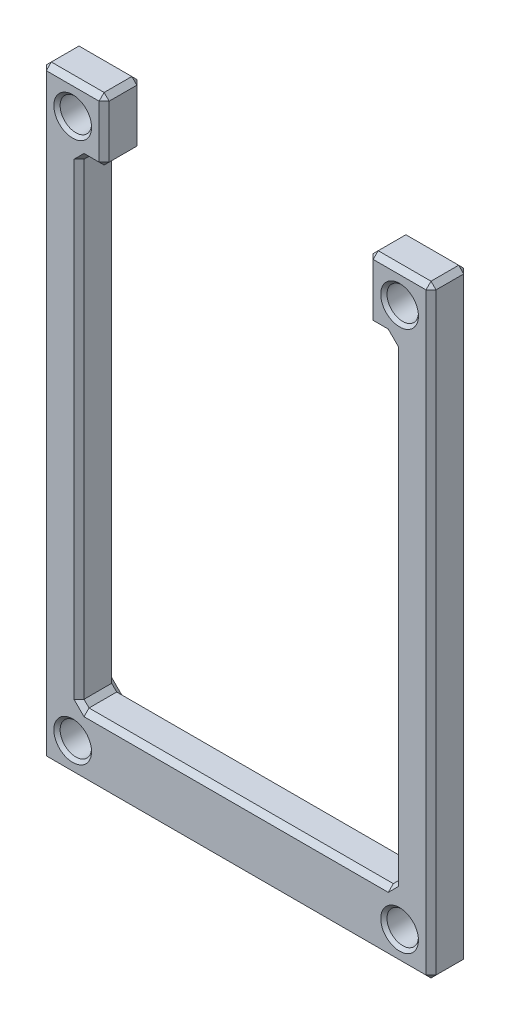
SolidWorks part; units mm, degrees
ref_plane "Ebene vorne" through (0, 0, 0) normal (1, 0, 0) x (0, 1, 0)
ref_plane "Ebene oben" through (0, 0, 0) normal (0, 0, 1) x (0, 1, 0)
ref_plane "Ebene rechts" through (0, 0, 0) normal (0, 1, 0) x (-1, 0, 0)
sketch "Skizze1" plane through (0, 0, 0) normal (0, 0, 1) x (0, 1, 0)
  line L0 (-24, 15.5) -> (24, 15.5)
  line L1 (24, 15.5) -> (24, 10.5)
  line L2 (24, 10.5) -> (-19, 10.5)
  line L3 (-19, 10.5) -> (-19, -10.5)
  line L4 (-19, -10.5) -> (24, -10.5)
  line L5 (24, -10.5) -> (24, -15.5)
  line L6 (24, -15.5) -> (-24, -15.5)
  line L7 (-24, -15.5) -> (-24, 15.5)
  line L8 (0, 15.5) -> (0, 0) construction
  line L9 (-24, 0) -> (0, 0) construction
  dimension "D1" = 48
  dimension "D2" = 31
  dimension "D3" = 5
  dimension "D4" = 5
extrude "Aufsatz-Linear austragen1" add sketch "Skizze1" along normal mid plane 3
hole_wizard "Ø2.5 (2.5) Durchmesser Bohrung1" positions "Skizze2" profile "Skizze3" hole size "Ø2.5" standard "DIN" end condition up to next
sketch "Skizze2" plane through (0, 0, 1.5) normal (0, 0, 1) x (0, -1, 0)
  line L1 (21.5, -13) -> (-21.5, -13) construction
  line L2 (21.5, -13) -> (21.5, 13) construction
  line L3 (21.5, 13) -> (-21.5, 13) construction
  line L4 (-21.5, -13) -> (-21.5, 13) construction
  line L5 (21.5, -13) -> (-21.5, 13) construction
  line L6 (21.5, 13) -> (-21.5, -13) construction
  point P1 (0, 0)
  point P2 (-21.5, 13)
  point P105 (21.5, -13)
  point P106 (21.5, 13)
  point P107 (-21.5, -13)
  dimension "D1" = 43
  dimension "D2" = 26
sketch "Skizze3" plane through (0, 0, 1.5) normal (1, 0, 0) x (0, -1, 0)
  line L0 (0, 0) -> (0, 3)
  line L1 (0, 3) -> (1.5, 3)
  line L2 (1.25, 2.75) -> (1.25, 0.25)
  line L3 (1.25, 0.25) -> (1.5, 0)
  line L5 (1.5, 0) -> (0, 0)
  line L6 (-1.25, 0.25) -> (-1.5, 0) construction
  line L7 (1.5, 3) -> (1.25, 2.75)
  line L8 (-1.5, 3) -> (-1.25, 2.75) construction
  line L11 (0, -6.35) -> (0, 107.95) construction
  dimension "Bohrerdurchmesser" = 2.5
  dimension "Bohrungstiefe" = 3
  dimension "Senkdurchmesser2 (Oben)" = 3
  dimension "Senkwinkel2 (Oben)" = 90
  dimension "Senkdurchmesser2 (Unten)" = 3
  dimension "Senkwinkel2 (Unten)" = 90
sketch "Skizze4" plane through (0, 0, 1.5) normal (0, 0, 1) x (1, 0, 0)
  line L0 (10.5, -19) -> (-10.5, -19) construction
  line L1 (12.5, -19) -> (-12.5, -19)
  line L2 (12.5, -19) -> (12.5, 19)
  line L3 (12.5, 19) -> (-12.5, 19)
  line L4 (-12.5, -19) -> (-12.5, 19)
  line L5 (12.5, -19) -> (-12.5, 19) construction
  line L6 (12.5, 19) -> (-12.5, -19) construction
  point P0 (0, 0)
  point P6 (0, -19)
  dimension "D2" = 25
extrude "Schnitt-Linear austragen1" cut sketch "Skizze4" against normal up to surface (3 mm away) up to face at (14.5, 21.5, -1.5)
chamfer "Fase1" distance 0.4 angle 45 36 edges at (-10.5, 21.5, 1.5) (-10.5, 21.5, -1.5) (-10.5, 24, 0) (-13, 24, 1.5) (-13, 24, -1.5) (13, 24, 1.5) (15.5, 0, 1.5) (15.5, 24, 0) (-15.5, 24, 0) (-15.5, 0, 1.5) (-15.5, 0, -1.5) (-15.5, -24, 0) (0, -24, 1.5) (15.5, -24, 0) (0, -24, -1.5) (15.5, 0, -1.5) (13, 24, -1.5) (10.5, 24, 0) (10.5, 21.5, 1.5) (10.5, 21.5, -1.5) (-11.5, 19, -1.5) (-11.5, 19, 1.5) (-12.5, 0, -1.5) (-12.5, -19, 0) (-12.5, 0, 1.5) (-12.5, 19, 0) (0, -19, -1.5) (11.5, 19, -1.5) (11.5, 19, 1.5) (0, -19, 1.5) (12.5, 0, -1.5) (12.5, 19, 0) (12.5, 0, 1.5) (12.5, -19, 0) (10.5, 19, 0) (-10.5, 19, 0)
